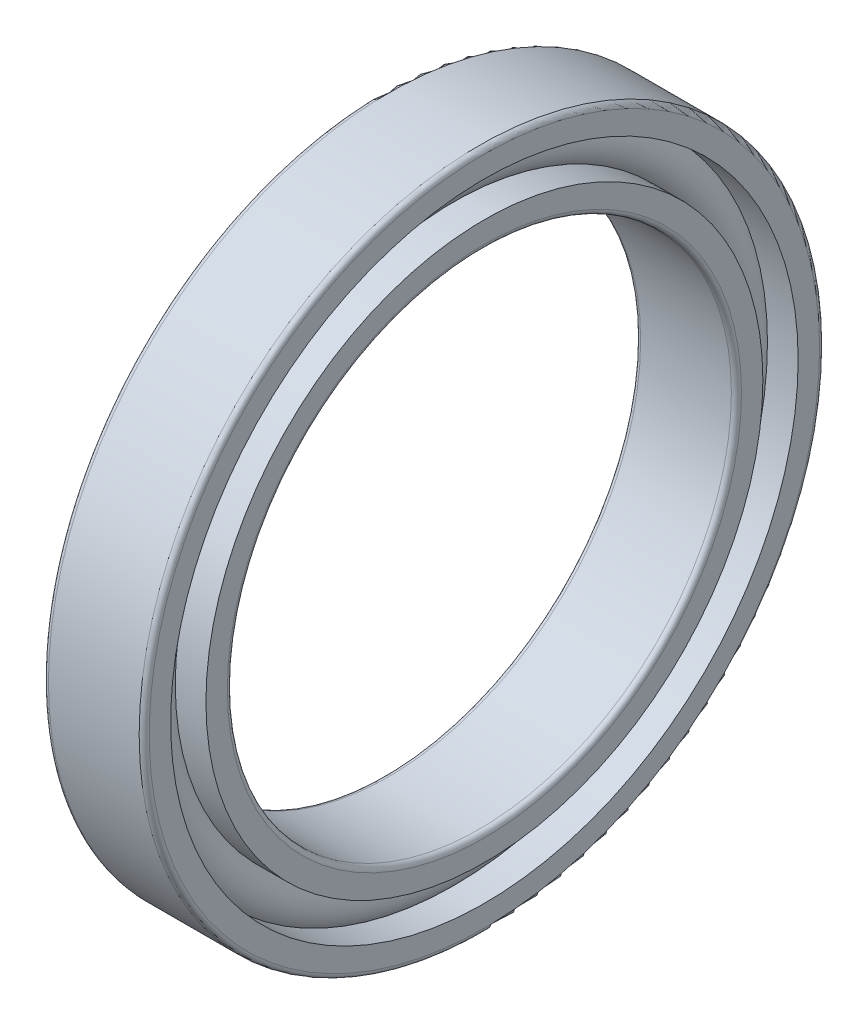
SolidWorks part; units mm, degrees
ref_plane "Plane1" through (0, 0, 0) normal (0, 0, 1) x (1, 0, 0)
ref_plane "Plane2" through (0, 0, 0) normal (0, 1, 0) x (1, 0, 0)
ref_plane "Plane3" through (0, 0, 0) normal (1, 0, 0) x (0, 0, -1)
other "Configuration Table"
sketch "Clipboard" plane through (0, 0, 0) normal (0, 0, 1) x (1, 0, 0)
  line L0 (-10, 0) -> (10, 0) construction
  line L1 (0, 0) -> (22.3471, -0.7804)
  line L2 (0, 0) -> (11.7428, 0.4101)
  line L3 (0, 0) -> (22.3471, -0.7804)
  line L4 (0, 0) -> (-22.3573, -0.3902)
  dimension "BallCLRad" = 11.75
sketch "CagSpiSke" plane through (0, 0, 0) normal (0, 0, 1) x (1, 0, 0)
  line L0 (0.105, 11.575) -> (0.105, 11.925)
  line L1 (0.105, 11.925) -> (-0.105, 11.925)
  line L2 (-0.105, 11.925) -> (-0.105, 11.575)
  line L3 (-0.105, 11.575) -> (0.105, 11.575)
  line L4 (-20.6375, 0) -> (20.6375, 0) construction
  line L5 (0, 0) -> (0, 23.7692) construction
  dimension "OD" = 23.85
  dimension "ID" = 23.15
revolve "CageSpine" add sketch "CagSpiSke" angle 0.001 about L4 reverse direction yes
ref_axis "Axis1" through (-50, 0, 0) along (1, 0, 0)
sketch "CagBalSke" plane through (0, 0, 0) normal (0, 0, 1) x (1, 0, 0)
  line L0 (-1.155, 11.75) -> (1.155, 11.75)
  line L1 (-1.905, 11.75) -> (1.905, 11.75) construction
  line L2 (-10, 0) -> (10, 0) construction
  line L3 (0, 0) -> (0, 24) construction
  arc A0 (1.155, 11.75) -> (-1.155, 11.75) centre (0, 11.75) cw
  dimension "BallCLRad" = 11.75
revolve "CageBall" [suppressed] add sketch "CagBalSke" angle 360 about L1 reverse direction yes
pattern_circular "CageBalls" [suppressed] count 2 every 180 about axis through (-50, 0, 0) along (1, 0, 0)
sketch "CagTrmODSke" plane through (0, 0, 0) normal (0, 0, 1) x (1, 0, 0)
  line L0 (1.156, 11.925) -> (1.156, 12.906)
  line L1 (1.156, 12.906) -> (-1.156, 12.906)
  line L2 (-1.156, 12.906) -> (-1.156, 11.925)
  line L3 (-1.156, 11.925) -> (1.156, 11.925)
  line L4 (-20.6375, 0) -> (20.6375, 0) construction
  line L5 (0, 0) -> (0, 25) construction
  dimension "Width" = 2.312
  dimension "ID" = 23.85
  dimension "OD" = 25.812
revolve "CageTrimOD" [suppressed] cut sketch "CagTrmODSke" angle 360 about L4 reverse direction yes
sketch "CagTrmIDSke" plane through (0, 0, 0) normal (0, 0, 1) x (1, 0, 0)
  line L0 (1.156, 10.596) -> (1.156, 11.575)
  line L1 (1.156, 11.575) -> (-1.156, 11.575)
  line L2 (-1.156, 11.575) -> (-1.156, 10.596)
  line L3 (-1.156, 10.596) -> (1.156, 10.596)
  line L4 (-20.6375, 0) -> (20.6375, 0) construction
  line L5 (0, 0) -> (0, 25) construction
  dimension "Width" = 2.312
  dimension "ID" = 21.192
  dimension "OD" = 23.15
revolve "CageTrimID" [suppressed] cut sketch "CagTrmIDSke" angle 360 about L4 reverse direction yes
sketch "BalSimSke" plane through (0, 0, 0) normal (0, 0, 1) x (1, 0, 0)
  line L0 (-10, 0) -> (10, 0) construction
  line L1 (-10, 11.75) -> (10, 11.75) construction
  line L2 (0, 0) -> (0, 23) construction
  circle A0 centre (0, 11.75) radius 1.05
  dimension "BallCLRad" = 11.75
  dimension "Ball_diameter" = 2.1
revolve "BallsSimplified" add sketch "BalSimSke" angle 360 about L0
sketch "BalDetSke" plane through (0, 0, 0) normal (0, 0, 1) x (1, 0, 0)
  line L0 (-1.05, 11.75) -> (1.05, 11.75)
  line L1 (-1.905, 11.75) -> (1.905, 11.75) construction
  line L2 (0, 0) -> (0, 25) construction
  arc A0 (1.05, 11.75) -> (-1.05, 11.75) centre (0, 11.75) cw
  dimension "BallCLRad" = 11.75
  dimension "Ball_diameter" = 2.1
revolve "BallDetailed" [suppressed] add sketch "BalDetSke" angle 360 about L1 reverse direction yes
sketch "InnRacSke" plane through (0, 0, 0) normal (0, 0, 1) x (1, 0, 0)
  line L0 (-0.7487, 11.05) -> (-2, 11.05)
  line L1 (-2, 11.05) -> (-2, 10.2)
  line L2 (-1.8, 10) -> (1.8, 10)
  line L3 (2, 10.2) -> (2, 11.05)
  line L4 (2, 11.05) -> (0.7487, 11.05)
  line L5 (-20.6375, 0) -> (20.6375, 0) construction
  line L6 (0, 0) -> (0, 30) construction
  arc A0 (-2, 10.2) -> (-1.8, 10) centre (-1.8, 10.2) ccw
  arc A1 (1.8, 10) -> (2, 10.2) centre (1.8, 10.2) ccw
  arc A2 (0.7487, 11.05) -> (-0.7487, 11.05) centre (0, 11.75) cw
  dimension "BallCLRad" = 11.75
  dimension "Fillet_radius" = 0.2
  dimension "Ball_diameter" = 2.05
  dimension "ID" = 20
  dimension "OD" = 22.1
  dimension "Width" = 4
revolve "InnerRace" add sketch "InnRacSke" angle 360 about L5 reverse direction yes
sketch "OutRacSke" plane through (0, 0, 0) normal (0, 0, 1) x (1, 0, 0)
  line L0 (-0.7487, 12.45) -> (-2, 12.45)
  line L1 (-2, 12.45) -> (-2, 13.3)
  line L2 (-1.8, 13.5) -> (1.8, 13.5)
  line L3 (2, 13.3) -> (2, 12.45)
  line L4 (2, 12.45) -> (0.7487, 12.45)
  line L5 (-20.6375, 0) -> (20.6375, 0) construction
  line L6 (0, 0) -> (0, 30) construction
  arc A0 (-2, 13.3) -> (-1.8, 13.5) centre (-1.8, 13.3) cw
  arc A1 (1.8, 13.5) -> (2, 13.3) centre (1.8, 13.3) cw
  arc A2 (0.7487, 12.45) -> (-0.7487, 12.45) centre (0, 11.75) ccw
  dimension "BallCLRad" = 11.75
  dimension "Fillet_radius" = 0.2
  dimension "Ball_diameter" = 2.05
  dimension "Width" = 4
revolve "OuterRace" add sketch "OutRacSke" angle 360 about L5 reverse direction yes
pattern_circular "BallsDetailed" [suppressed] count 2 every 180 about axis through (-50, 0, 0) along (1, 0, 0)
equation "\"BallCLRad@Clipboard\" = ( \"OD@OutRacSke\" + \"ID@InnRacSke\" ) / 4"
equation "\"BallCLRad@BalSimSke\" = \"BallCLRad@Clipboard\""
equation "\"BallCLRad@BalDetSke\" = \"BallCLRad@Clipboard\""
equation "\"BallCLRad@InnRacSke\" = \"BallCLRad@Clipboard\""
equation "\"BallCLRad@OutRacSke\" = \"BallCLRad@Clipboard\""
equation "\"Ball_diameter@InnRacSke\" = \"Ball_diameter@BalDetSke\" - 0.05"
equation "\"Ball_diameter@OutRacSke\" = \"Ball_diameter@BalDetSke\" - 0.05"
equation "\"Ball_diameter@BalSimSke\" = \"Ball_diameter@BalDetSke\""
equation "\"Width@OutRacSke\" = \"Width@InnRacSke\""
equation "\"Fillet_radius@OutRacSke\" = \"Fillet_radius@InnRacSke\""
equation "\"Max_count@Clipboard\" = int( 3.14159265 / atn(( \"Ball_diameter@BalDetSke\" / 2) / sqr( \"BallCLRad@Clipboard\"  *  \"BallCLRad@Clipboard\" - ( \"Ball_diameter@BalDetSke\" / 2) *  ( \"Ball_diameter@BalDetSke\" / 2))))"
equation "\"Max_count@Clipboard\" = ((sgn( \"Max_count@Clipboard\" - \"Count@Clipboard\" )-1)*( \"Max_count@Clipboard\" - \"Count@Clipboard\" ))/-2+ \"Count@Clipboard\""
equation "\"Count@BallsDetailed\" = int( \"Show_count@Clipboard\" ) "
equation "\"Count@BallsDetailed\" = ((sgn( \"Count@BallsDetailed\" - \"Max_count@Clipboard\" )-1)*( \"Count@BallsDetailed\" - \"Max_count@Clipboard\" ))/-2+ \"Max_count@Clipboard\""
equation "\"Count@BallsDetailed\" = ((sgn( \"Count@BallsDetailed\" - \"Min_count@Clipboard\" )+1)*( \"Count@BallsDetailed\" - \"Min_count@Clipboard\"))/2 +\"Min_count@Clipboard\""
equation "\"Angle@BallsDetailed\" = 360.0 / \"Max_count@Clipboard\""
equation "\"BallCLRad@CagBalSke\" = \"BallCLRad@Clipboard\""
equation "\"Count@CageBalls\" = \"Count@BallsDetailed\""
equation "\"Angle@CageBalls\" = \"Angle@BallsDetailed\""
equation "\"Angle@CageSpine\" =  \"Angle@CageBalls\" * ( \"Count@CageBalls\" -1 + int( \"Count@CageBalls\" / \"Max_count@Clipboard\" ) )  + 0.001 -  int( \"Count@CageBalls\" / \"Max_count@Clipboard\" ) * 0.001"
equation "\"Angle@CageSpine\" =  \"Angle@CageSpine\" * int( \"Min_count@Clipboard\" / 2) + int(1 / \"Min_count@Clipboard\")  * 0.001"
equation "\"CageWallOD@CagBalSke\" =  \"Ball_diameter@BalDetSke\" * 1.1"
equation "\"Thickness@CagSpiSke\" =  \"Ball_diameter@BalDetSke\" * 0.1"
equation "\"OD@CagTrmODSke\" = \"BallCLRad@Clipboard\" * 2 + \"CageWallOD@CagBalSke\" + 0.002"
equation "\"ID@CagTrmODSke\" = \"BallCLRad@Clipboard\" * 2 + \"Ball_diameter@BalDetSke\" / 6"
equation "\"OD@CagTrmIDSke\" = \"BallCLRad@Clipboard\" * 2 - \"Ball_diameter@BalDetSke\" / 6"
equation "\"ID@CagTrmIDSke\" = \"BallCLRad@Clipboard\" * 2 - \"CageWallOD@CagBalSke\" + 0.002"
equation "\"OD@CagSpiSke\" = \"ID@CagTrmODSke\""
equation "\"ID@CagSpiSke\" = \"OD@CagTrmIDSke\""
equation "\"Width@CagTrmODSke\" = \"CageWallOD@CagBalSke\" + 0.002"
equation "\"Width@CagTrmIDSke\" = \"CageWallOD@CagBalSke\" + 0.002"
